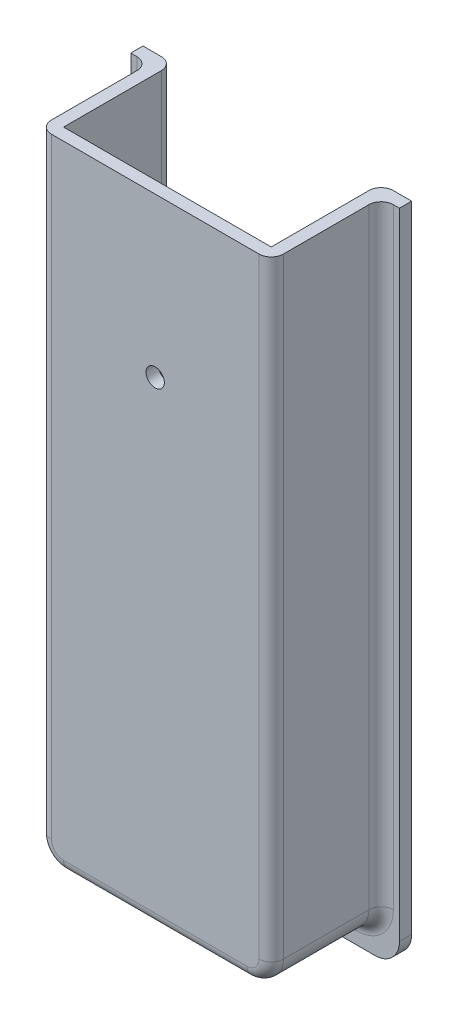
SolidWorks part; units mm, degrees
ref_plane "Plan de face" through (0, 0, 0) normal (0, 0, 1) x (1, 0, 0)
ref_plane "Plan de dessus" through (0, 0, 0) normal (0, 1, 0) x (1, 0, 0)
ref_plane "Plan de droite" through (0, 0, 0) normal (1, 0, 0) x (0, 0, -1)
sketch "Esquisse1" plane through (0, 0, 0) normal (0, 0, 1) x (1, 0, 0)
  line L1 (0, 0) -> (34, 0)
  line L2 (0, 0) -> (0, 100)
  line L3 (0, 100) -> (34, 100)
  line L4 (34, 0) -> (34, 100)
  dimension "D1" = 34
  dimension "D2" = 100
extrude "Boss.-Extru.1" add sketch "Esquisse1" along normal blind 18
shell "Coque1" thickness 2 removed face at (17, 50, 0) outward yes
sketch "Esquisse2" plane through (0, 100, 0) normal (0, -1, 0) x (1, 0, 0)
  line L1 (34, 0) -> (0, 0)
  line L2 (34, 0) -> (34, 18)
  line L3 (34, 18) -> (0, 18)
  line L4 (0, 0) -> (0, 18)
extrude "Enlèv. mat.-Extru.1" cut sketch "Esquisse2" against normal blind 18
fillet "Congé1" radius 2 3 edges at (17, -2, 20) (36, 50, 20) (-2, 50, 20)
sketch "Esquisse3" plane through (0, 0, 0) normal (0, 0, -1) x (-1, 0, 0)
  line L0 (-36, 50) -> (2, 50) construction
  line L1 (-36, -2) -> (-36, 102) construction
  line L2 (2, 102) -> (2, -2) construction
  line L3 (-17, 50) -> (-17, 102) construction
  line L4 (-34, 102) -> (0, 102) construction
ref_axis "Axe1" through (17, 50, 0) along (0, 1, 0)
sketch "Esquisse4" plane through (0, 0, 0) normal (0, 0, -1) x (-1, 0, 0)
  line L0 (-36, 102) -> (2, 102) construction
  line L1 (2, -2) -> (2, 102) construction
sketch "Esquisse5" plane through (-2, 0, 0) normal (-1, 0, 0) x (0, 0, 1)
  line L0 (18, 102) -> (0, 102) construction
  line L1 (0, -2) -> (1.9997, -2)
  line L2 (0, -2) -> (0, 102)
  line L3 (0, 102) -> (1.9997, 102)
  line L4 (1.9997, -2) -> (1.9997, 102)
sketch "Esquisse6" plane through (36, 0, 0) normal (1, 0, 0) x (0, 0, -1)
  line L1 (0, 102) -> (-1.9997, 102)
  line L2 (0, 102) -> (0, -2)
  line L3 (0, -2) -> (-1.9997, -2)
  line L4 (-1.9997, 102) -> (-1.9997, -2)
extrude "Boss.-Extru.2" add sketch "Esquisse5" along normal up to surface (3 mm away)
extrude "Boss.-Extru.3" add sketch "Esquisse6" along normal up to surface (3 mm away)
sketch "Esquisse7" plane through (0, -2, 0) normal (0, -1, 0) x (1, 0, 0)
  line L0 (-5, 1.9997) -> (-5, 0) construction
  line L1 (-5, 1.9997) -> (39, 1.9997)
  line L2 (-5, 1.9997) -> (-5, 0)
  line L3 (-5, 0) -> (39, 0)
  line L4 (39, 1.9997) -> (39, 0)
  line L5 (39, 0) -> (39, 1.9997) construction
extrude "Boss.-Extru.4" add sketch "Esquisse7" along normal up to surface (4 mm away)
fillet "Congé2" radius 4 6 edges at (-1.4142, -1.4142, 19.4142) (35.4142, -1.4142, 19.4142) (36, -2, 9.9998) (-2, -2, 9.9998) (-5, -6, 0.9998) (39, -6, 0.9998)
fillet "Congé3" radius 2 5 edges at (36, 52, 1.9997) (34.8284, -0.8284, 1.9997) (17, -2, 1.9997) (-0.8284, -0.8284, 1.9997) (-2, 52, 1.9997)
sketch "Esquisse8" plane through (0, 0, 20) normal (0, 0, 1) x (1, 0, 0)
  circle A0 centre (17, 76) radius 1.5
  dimension "D1" = 3
fillet "Congé5" radius 2 3 edges at (34, 51, 0) (0, 51, 0) (17, 0, 0)
extrude "Enlèv. mat.-Extru.2" cut sketch "Esquisse8" against normal blind 10
